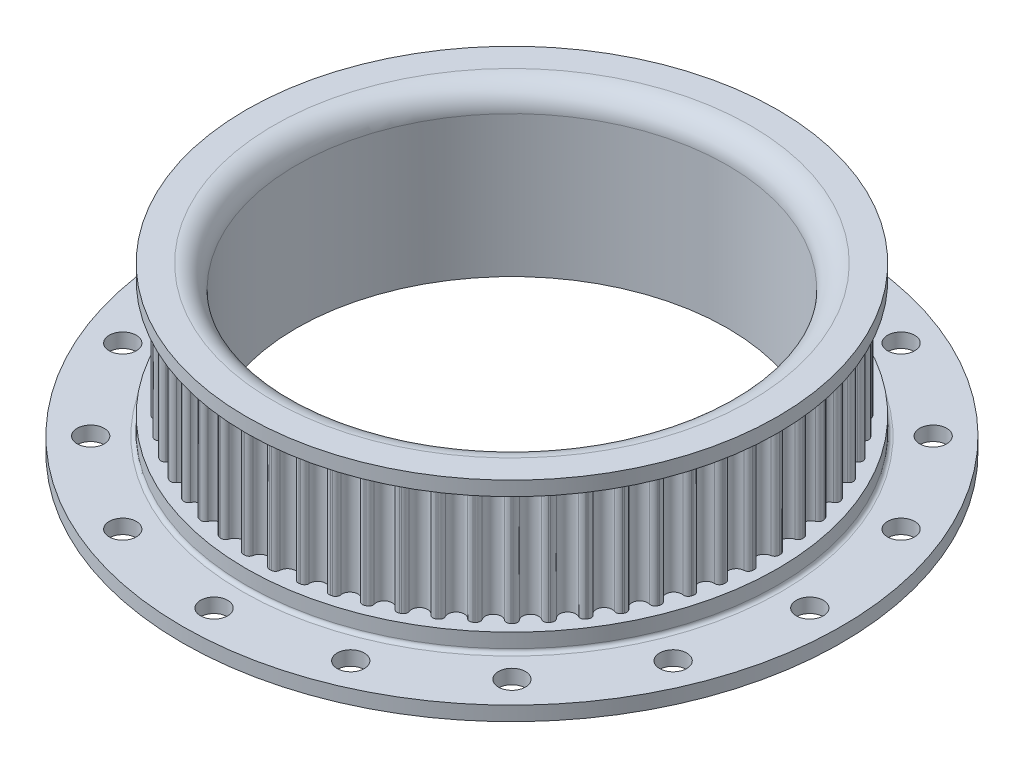
SolidWorks part; units mm, degrees
ref_plane "Front Plane" through (0, 0, 0) normal (0, 0, 1) x (1, 0, 0)
ref_plane "Top Plane" through (0, 0, 0) normal (0, 1, 0) x (1, 0, 0)
ref_plane "Right Plane" through (0, 0, 0) normal (1, 0, 0) x (0, 0, -1)
sketch "Sketch1" plane through (0, 0, 0) normal (0, 1, 0) x (1, 0, 0)
  line L0 (0, 0) -> (0, 28.2667) construction
  line L1 (0, 0) -> (2.9202, 27.7837) construction
  circle A0 centre (0, 0) radius 28.2667 construction
  circle A1 centre (0, 0) radius 27.0467 construction
  circle A2 centre (0, 27.9367) radius 0.89 construction
  circle A5 centre (2.9202, 27.7837) radius 0.89 construction
  arc A6 (0, 27.0467) -> (0.8804, 27.8061) centre (0, 27.9367) ccw
  arc A7 (0.8804, 27.8061) -> (1.3997, 28.2321) centre (1.3749, 27.7327) cw
  arc A8 (1.559, 28.2237) -> (2.031, 27.7458) centre (1.5314, 27.7245) cw
  arc A9 (2.8272, 26.8986) -> (2.031, 27.7458) centre (2.9202, 27.7837) cw
  arc A10 (1.3997, 28.2321) -> (1.559, 28.2237) centre (0, 0) cw
  arc A11 (0, 27.0467) -> (2.8272, 26.8986) centre (0, 0) ccw
  dimension "D1" = 56.5335
  dimension "D3" = 1.78
  dimension "D4" = 0.5
  dimension "D2" = 1.22
  dimension "D5" = 6
extrude "Boss-Extrude1" add sketch "Sketch1" along normal mid plane 13 contours A6 A11 A9 A8 A7 region at (0.001, 0, -0.0192)
ref_axis "Axis1" through (0, 3.3, 0) along (0, -1, 0)
pattern_circular "CirPattern1" count 60 over 360 about axis through (0, 3.3, 0) along (0, -1, 0) of "Boss-Extrude1"
sketch "Sketch2" plane through (0, 0, 0) normal (1, 0, 0) x (0, 0, -1)
  line L10 (0, 6.5) -> (29.4415, 6.5) construction
  line L11 (0, 6.5) -> (0, 8.0875) construction
  line L12 (0, 8.0875) -> (29.4415, 8.0875) construction
  line L15 (29.4415, 6.5) -> (29.4415, 8.0875) construction
  line L20 (0, 3.3) -> (0, -3.3) construction
  line L22 (29.4415, 8.0875) -> (0, 8.0875)
  line L23 (29.4415, 8.0875) -> (29.4415, 6.5)
  line L24 (29.4415, 6.5) -> (0, 6.5)
  line L25 (0, 8.0875) -> (0, 6.5)
  dimension "D1" = 1.5875
  dimension "D2" = 29.4415
  dimension "D3" = 6.5
revolve "Revolve3" add sketch "Sketch2" angle 360 about axis through (0, 3.3, 0) along (0, -1, 0) region at (0, 7.2937, -14.7207)
mirror "Mirror1" about plane through (0, 0, 0) normal (0, 1, 0) of "Revolve3"
sketch "Sketch3" plane through (0, 0, 0) normal (0, -1, 0) x (-1, 0, 0)
  circle A0 centre (0, 0) radius 23.8852
  dimension "D1" = 47.7705
extrude "Cut-Extrude1" cut sketch "Sketch3" against normal through all both and the other way through all
sketch "Sketch5" plane through (0, 0, 0) normal (0, 0, 1) x (1, 0, 0)
  line L0 (29.4415, -6.5) -> (-29.4415, -6.5) construction
  line L1 (-29.854, -8.5) -> (-36.5125, -8.5)
  line L2 (-36.5125, -8.5) -> (-36.5125, -10.0875)
  line L3 (-36.5125, -10.0875) -> (-23.8852, -10.0875)
  line L4 (-23.8852, -10.0875) -> (-23.8852, -8.0875)
  line L5 (-29.4415, -8.0875) -> (29.4415, -8.0875) construction
  line L6 (-23.8852, -8.0875) -> (-29.4415, -8.0875)
  arc A0 (-29.4415, -8.0875) -> (-29.854, -8.5) centre (-29.854, -8.0875) cw
  dimension "D1" = 2
  dimension "D2" = 36.5125
  dimension "D3" = 1.5875
revolve "Revolve4" add sketch "Sketch5" angle 360 about axis through (0, 3.3, 0) along (0, -1, 0)
sketch "Sketch6" plane through (0, -8.5, 0) normal (0, 1, 0) x (1, 0, 0)
  line L0 (-30.488, 12.6286) -> (0, 0) construction
  line L1 (0, 0) -> (-36.5125, 0) construction
  circle A0 centre (-30.488, 12.6286) radius 1.5
  circle A1 centre (0, 0) radius 36.5125 construction
  dimension "D2" = 3
  dimension "D1" = 33
  dimension "D3" = 22.5
extrude "Cut-Extrude2" cut sketch "Sketch6" against normal through all
pattern_circular "CirPattern2" count 16 over 360 about axis through (0, 3.3, 0) along (0, -1, 0) of "Cut-Extrude2"
fillet "Fillet1" radius 2.54 1 edges at (0, 8.0875, -23.8852)
sketch "Sketch9" plane through (0, -10.0875, 0) normal (0, -1, 0) x (1, 0, 0)
  circle A1 centre (0, 0) radius 36.5125
  circle A2 centre (0, 0) radius 29
  circle A3 centre (-30.488, -12.6286) radius 1.5
  circle A4 centre (-30.488, -12.6286) radius 1.5
  circle A5 centre (-23.3345, -23.3345) radius 1.5
  circle A6 centre (-23.3345, -23.3345) radius 1.5
  circle A7 centre (23.3345, 23.3345) radius 1.5
  circle A8 centre (23.3345, 23.3345) radius 1.5
  circle A9 centre (12.6286, 30.488) radius 1.5
  circle A10 centre (12.6286, 30.488) radius 1.5
  circle A11 centre (0, 33) radius 1.5
  circle A12 centre (0, 33) radius 1.5
  circle A13 centre (-12.6286, 30.488) radius 1.5
  circle A14 centre (-12.6286, 30.488) radius 1.5
  circle A15 centre (-23.3345, 23.3345) radius 1.5
  circle A16 centre (-23.3345, 23.3345) radius 1.5
  circle A17 centre (-30.488, 12.6286) radius 1.5
  circle A18 centre (-30.488, 12.6286) radius 1.5
  circle A19 centre (-33, 0) radius 1.5
  circle A20 centre (-33, 0) radius 1.5
  circle A21 centre (30.488, 12.6286) radius 1.5
  circle A22 centre (30.488, 12.6286) radius 1.5
  circle A23 centre (33, 0) radius 1.5
  circle A24 centre (33, 0) radius 1.5
  circle A25 centre (30.488, -12.6286) radius 1.5
  circle A26 centre (30.488, -12.6286) radius 1.5
  circle A27 centre (23.3345, -23.3345) radius 1.5
  circle A28 centre (23.3345, -23.3345) radius 1.5
  circle A29 centre (12.6286, -30.488) radius 1.5
  circle A30 centre (12.6286, -30.488) radius 1.5
  circle A31 centre (0, -33) radius 1.5
  circle A32 centre (0, -33) radius 1.5
  circle A33 centre (-12.6286, -30.488) radius 1.5
  circle A34 centre (-12.6286, -30.488) radius 1.5
  circle A35 centre (0, 0) radius 36.5125
  point P0 (0, 0)
  dimension "D18" = 58
  dimension "D2" = 0
  dimension "D3" = 0
  dimension "D4" = 0
  dimension "D5" = 0
  dimension "D6" = 0
  dimension "D7" = 0
  dimension "D8" = 0
  dimension "D9" = 0
  dimension "D10" = 0
  dimension "D11" = 0
  dimension "D12" = 0
  dimension "D13" = 0
  dimension "D14" = 0
  dimension "D15" = 0
  dimension "D16" = 0
  dimension "D17" = 0
  dimension "D19" = 0
equation "\"TEETH_NUM\"= 60"
equation "\"TOOTH_PITCH\"= 3mm"
equation "\"PITCH_LINE_OFFSET\"= .015in"
equation "\"DIAMETER_PER_GROOVE\"= \"OUTSIDE_DIAMETER\" / \"TEETH_NUM\" * 1in"
equation "\"PITCH_DIAMETER\"= ( ( \"TEETH_NUM\" * 3 - 1.31 ) / 3.1415 + .415 ) * 1mm"
equation "\"OUTSIDE_DIAMETER\"= \"PITCH_DIAMETER\" - \"PITCH_LINE_OFFSET\" * 2"
equation "\"D1@Sketch1\"=\"OUTSIDE_DIAMETER\""
equation "\"TOOTH_HEIGHT\"= 1.22mm"
equation "\"D2@Sketch1\"=\"TOOTH_HEIGHT\""
equation "\"TOOTH_DIAMETER\"= 1.78mm"
equation "\"INTERNAL_RADIUS\"= .5mm"
equation "\"D3@Sketch1\"=\"TOOTH_DIAMETER\""
equation "\"D5@Sketch1\"=360 / \"TEETH_NUM\""
equation "\"D4@Sketch1\"=\"INTERNAL_RADIUS\""
equation "\"D1@CirPattern1\"=\"TEETH_NUM\""
equation "\"BELT_GAP\"= 13mm"
equation "\"D2@Sketch2\"=\"PITCH_DIAMETER\"/2+1/32"
equation "\"D3@Sketch2\"=\"BELT_GAP\"/2"
equation "\"D1@Sketch3\"=\"PITCH_DIAMETER\"-.375"
equation "\"D1@Boss-Extrude1\"=\"BELT_GAP\""
equation "\"center_offset\"=0.75"
equation "\"Bearing_Diameter\"= 58mm"
equation "\"bolt_on_feature\"=16"
equation "\"D1@CirPattern2\"=\"bolt_on_feature\""
